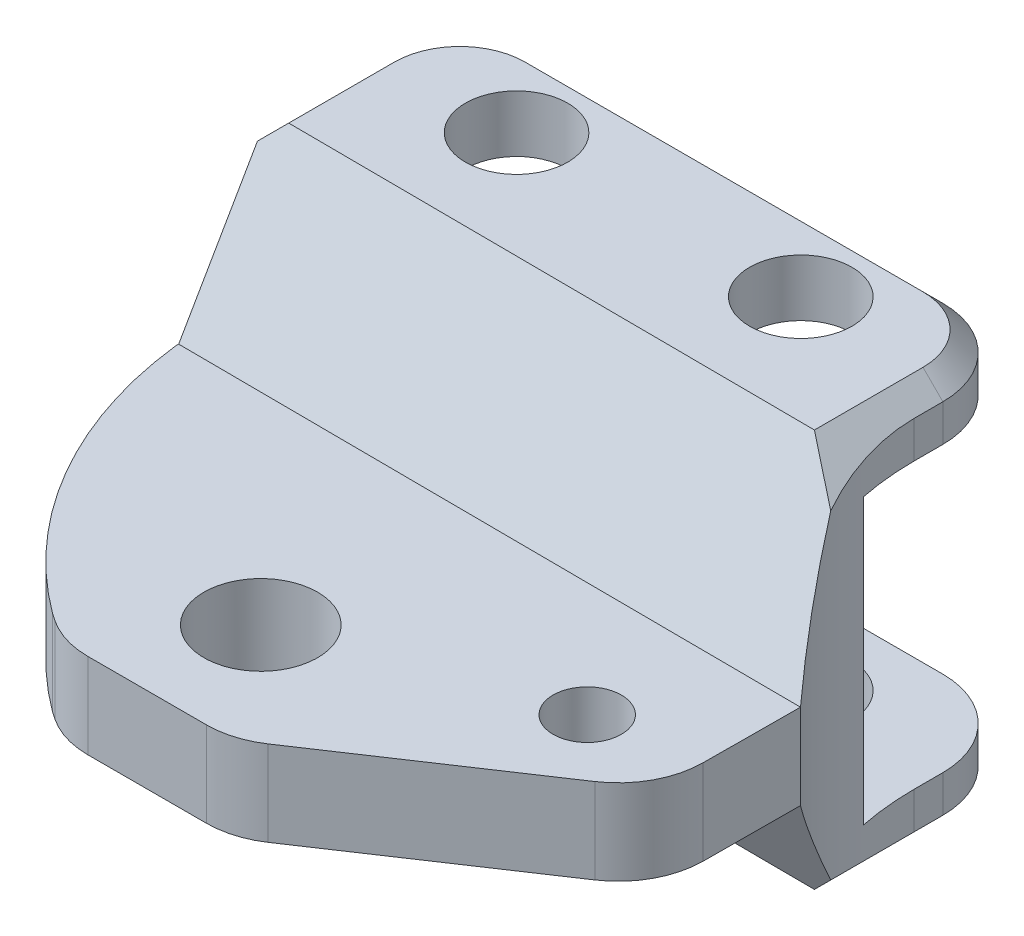
SolidWorks part; units mm, degrees
ref_plane "Front Plane" through (0, 0, 0) normal (0, 0, 1) x (1, 0, 0)
ref_plane "Top Plane" through (0, 0, 0) normal (0, 1, 0) x (1, 0, 0)
ref_plane "Right Plane" through (0, 0, 0) normal (1, 0, 0) x (0, 0, -1)
sketch "Sketch1" plane through (0, 0, 0) normal (0, 1, 0) x (1, 0, 0)
  line L14 (-10, 5) -> (10, 5)
  line L16 (-10, -5) -> (-10, 5)
  line L17 (-10, 5) -> (10, 5)
  line L18 (10, -5) -> (10, 5)
  line L19 (-10, -5) -> (10, 5) construction
  line L20 (-10, 5) -> (10, -5) construction
  line L21 (-10, 5) -> (-10, -1)
  line L22 (10, 5) -> (10, -1)
  line L23 (-10, -1) -> (10, -1)
  line L24 (-4.0048, -15.32) -> (-3, -16)
  line L27 (12, -5.0111) -> (11.9721, -10.0111)
  line L29 (10, -5) -> (12, -5.0111)
  line L30 (-3, -16) -> (3, -16)
  line L32 (3, -16) -> (11.9721, -10.0111)
  circle A5 centre (-5, 2) radius 1.8
  circle A6 centre (5, 2) radius 1.8
  circle A8 centre (0, -12) radius 2
  circle A10 centre (8.4777, -8.9916) radius 1.2
  arc A12 (-10, -5) -> (-3, -16) centre (4.8972, -3.2472) ccw
  point P0 (0, 0)
  point P1 (0, 0)
  point P14 (0, -16)
  dimension "D3" = 6
  dimension "D4" = 3.6
  dimension "D1" = 10
  dimension "D2" = 20
  dimension "D8" = 2.4
  dimension "D9" = 4
  dimension "D12" = 15
  dimension "D5" = 5
  dimension "D6" = 5
  dimension "D7" = 3
  dimension "D10" = 12
  dimension "D11" = 1.5223
  dimension "D14" = 2
  dimension "D16" = 5
  dimension "D17" = 6
  dimension "D18" = 4
extrude "Boss-Extrude1" add sketch "Sketch1" along normal mid plane 14 contours L23 L16 L18 | L16 L23 L18 L14 | A8 region at (0, 0, -2) region at (0.6453, 0, 7.438)
extrude "Cut-Extrude1" cut sketch "Sketch1<3>" against normal mid plane 10 contours L16 L23 L18 L14 region at (0, 0, -2)
sketch "Sketch1<3>" plane through (0, 0, 0) normal (0, 1, 0) x (1, 0, 0) same geometry as "Sketch1"
fillet "Fillet1" radius 3 2 edges at (-10, 6, -5) (10, 6, -5)
chamfer "Chamfer3" distance 0.7 angle 45 10 edges at (-10, 7, 1.5) (-9.1213, 7, -4.1213) (0, 7, -5) (9.1213, 7, -4.1213) (10, 7, 1.5) (-10, -7, 1.5) (-9.1213, -7, -4.1213) (0, -7, -5) (9.1213, -7, -4.1213) (10, -7, 1.5)
sketch "Sketch2" plane through (12.0275, 0, 0.067) normal (1, 0, 0.0056) x (0.0056, 0, -1)
  line L1 (-15.983, -7) -> (-9.9442, -7) construction
  line L2 (-20.023, 1.5) -> (-20.023, 7)
  line L3 (-4.9442, 7) -> (-9.9442, 7) construction
  line L4 (-20.023, 7) -> (-1.7688, 7)
  line L5 (-20.0504, -7) -> (-20.0504, -1.5)
  line L7 (-1.7688, -7) -> (-20.0504, -7)
  line L8 (-20.023, 1.5) -> (-4.9442, 1.5)
  line L9 (-4.9442, 1.5) -> (-1.7688, 7)
  line L10 (-20.0504, -1.5) -> (-4.9442, -1.5)
  line L11 (-4.9442, -1.5) -> (-1.7688, -7)
  line L13 (-4.9442, 7) -> (2.0518, 7) construction
  line L14 (-4.9442, 7) -> (-4.9442, -7) construction
  dimension "D1" = 5.5
  dimension "D2" = 5.5
  dimension "D3" = 120
  dimension "D4" = 120
extrude "Cut-Extrude2" cut sketch "Sketch2" against normal through all
fillet "Fillet2" radius 10 1 edges at (10, 0, 5)
fillet "Fillet3" radius 3 3 edges at (-3, 0, 16) (3, 0, 16) (11.9721, 0, 10.0111)
